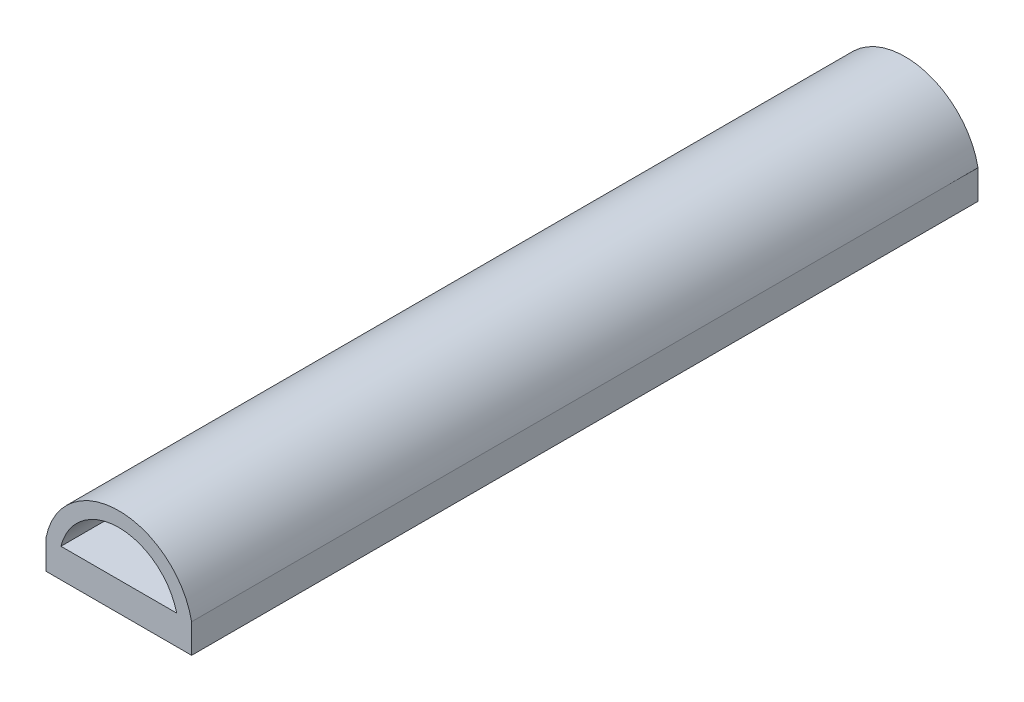
SolidWorks part; units mm, degrees
ref_plane "Front Plane" through (0, 0, 0) normal (0, 0, 1) x (1, 0, 0)
ref_plane "Top Plane" through (0, 0, 0) normal (0, 1, 0) x (1, 0, 0)
ref_plane "Right Plane" through (0, 0, 0) normal (1, 0, 0) x (0, 0, -1)
sketch "Sketch1" plane through (0, 0, 0) normal (0, 0, 1) x (1, 0, 0)
  line L0 (-6.35, 1.2591) -> (-6.35, -1.2809)
  line L1 (-6.35, -1.2809) -> (6.35, -1.2809)
  line L3 (6.35, -1.2809) -> (6.35, 1.2591)
  line L39 (-5.049, 1.2591) -> (5.049, 1.2591)
  arc A0 (-6.35, 1.2591) -> (6.35, 1.2591) centre (0, 0) cw
  arc A3 (-5.049, 1.2591) -> (5.049, 1.2591) centre (0, 0) cw
  point P8 (0, 0)
  point P9 (6.4266, 1.9455)
  point P10 (0, 0)
  point P11 (6.35, 0)
  point P12 (0, 0)
  point P13 (-6.35, 3.9638)
  point P14 (5.6273, 2.9421)
  point P15 (0, 0)
  point P16 (-5.2833, 3.5226)
  dimension "D2" = 1.27
  dimension "D4" = 6.4736
  dimension "D1" = 12.7
  dimension "D3" = 2.54
extrude "Boss-Extrude1" add sketch "Sketch1" along normal blind 68.58
sketch "Sketch3" plane through (0, 0, 0) normal (0, 0, -1) x (-1, 0, 0)
  line L0 (0.508, -1.2809) -> (0.508, -3.3764)
  line L1 (0.508, -3.3764) -> (1.0795, -3.3764)
  line L2 (1.0795, -3.3764) -> (1.0795, -4.2654)
  line L3 (1.0795, -4.2654) -> (-1.0795, -4.2654)
  line L4 (-1.0795, -4.2654) -> (-1.0795, -3.3764)
  line L5 (-1.0795, -3.3764) -> (-0.508, -3.3764)
  line L6 (-0.508, -3.3764) -> (-0.508, -1.2809)
  line L7 (-0.508, -1.2809) -> (0.508, -1.2809)
  line L9 (6.35, -1.2809) -> (-6.35, -1.2809) construction
  point P10 (0, -1.2809)
  dimension "D1" = 2.0955
  dimension "D2" = 2.159
  dimension "D3" = 1.016
  dimension "D4" = 0.889
extrude "Boss-Extrude2" add sketch "Sketch3" against normal blind 25.4
